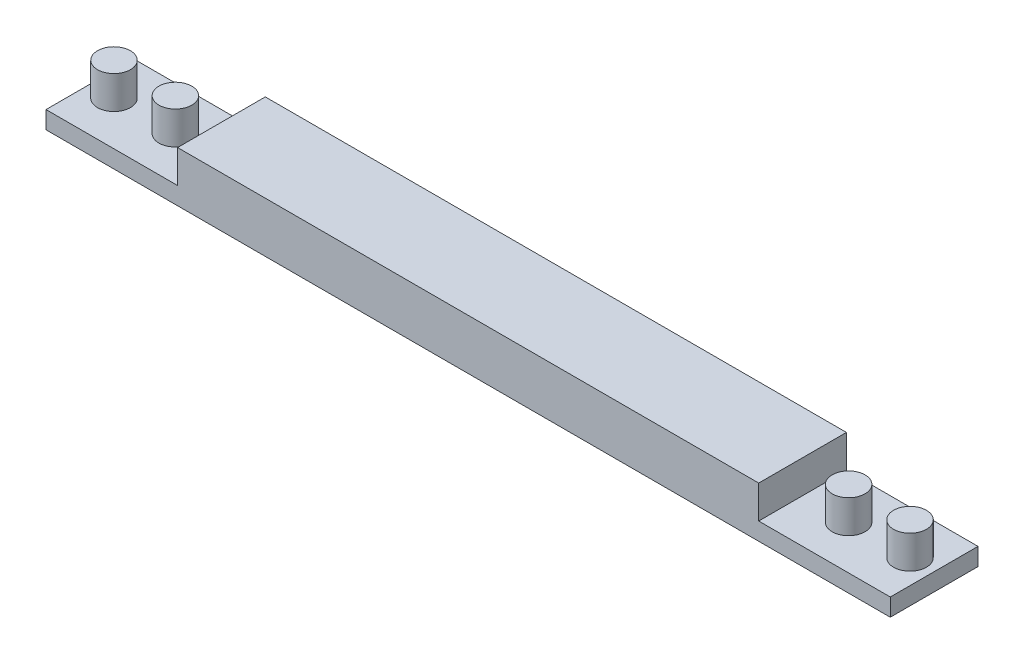
SolidWorks part; units mm, degrees
ref_plane "Спереди" through (0, 0, 0) normal (0, 0, 1) x (1, 0, 0)
ref_plane "Сверху" through (0, 0, 0) normal (0, 1, 0) x (1, 0, 0)
ref_plane "Справа" through (0, 0, 0) normal (1, 0, 0) x (0, 0, -1)
sketch "Эскиз1" plane through (0, 0, 0) normal (0, 1, 0) x (1, 0, 0)
  line L1 (-19.25, -2) -> (19.25, -2)
  line L2 (-19.25, -2) -> (-19.25, 2)
  line L3 (-19.25, 2) -> (19.25, 2)
  line L4 (19.25, -2) -> (19.25, 2)
  line L5 (-19.25, -2) -> (19.25, 2) construction
  line L6 (-19.25, 2) -> (19.25, -2) construction
  line L7 (-13.25, -2) -> (13.25, -2)
  line L8 (-13.25, -2) -> (-13.25, 2)
  line L9 (-13.25, 2) -> (13.25, 2)
  line L10 (13.25, -2) -> (13.25, 2)
  line L11 (-13.25, -2) -> (13.25, 2) construction
  line L12 (-13.25, 2) -> (13.25, -2) construction
  point P0 (0, 0)
  point P6 (0, 0)
  dimension "D1" = 4
  dimension "D2" = 38.5
  dimension "D3" = 26.5
extrude "Бобышка-Вытянуть1" add sketch "Эскиз1" along normal blind 0.8 contours L1 L10 L3 L8 | L1 L8 L3 L2 | L10 L1 L4 L3 region at (-16.25, 0, 0) region at (0, 0, 0) region at (16.25, 0, 0)
extrude "Бобышка-Вытянуть2" add sketch "Эскиз1<3>" along normal blind 1.5 from surface contours L1 L10 L3 L8 region at (0, 0, 0) starting at face at (0, 0.8, 0)
sketch "Эскиз1<3>" plane through (0, 0, 0) normal (0, 1, 0) x (1, 0, 0) same geometry as "Эскиз1"
sketch "Эскиз2" plane through (0, 0.8, 0) normal (0, 1, 0) x (1, 0, 0)
  line L1 (0, 7.0186) -> (0, -4.9291) construction
  line L2 (-19.25, -2) -> (-19.25, 2) construction
  circle A0 centre (-15.35, 0) radius 0.75
  circle A1 centre (-18.15, 0) radius 0.75
  circle A2 centre (18.15, 0) radius 0.75
  circle A3 centre (15.35, 0) radius 0.75
  point P4 (-19.25, 0)
  dimension "D3" = 2.8
  dimension "D4" = 1.5
  dimension "D1" = 1.1
  dimension "D2" = 2
extrude "Бобышка-Вытянуть3" add sketch "Эскиз2" along normal blind 1.5
